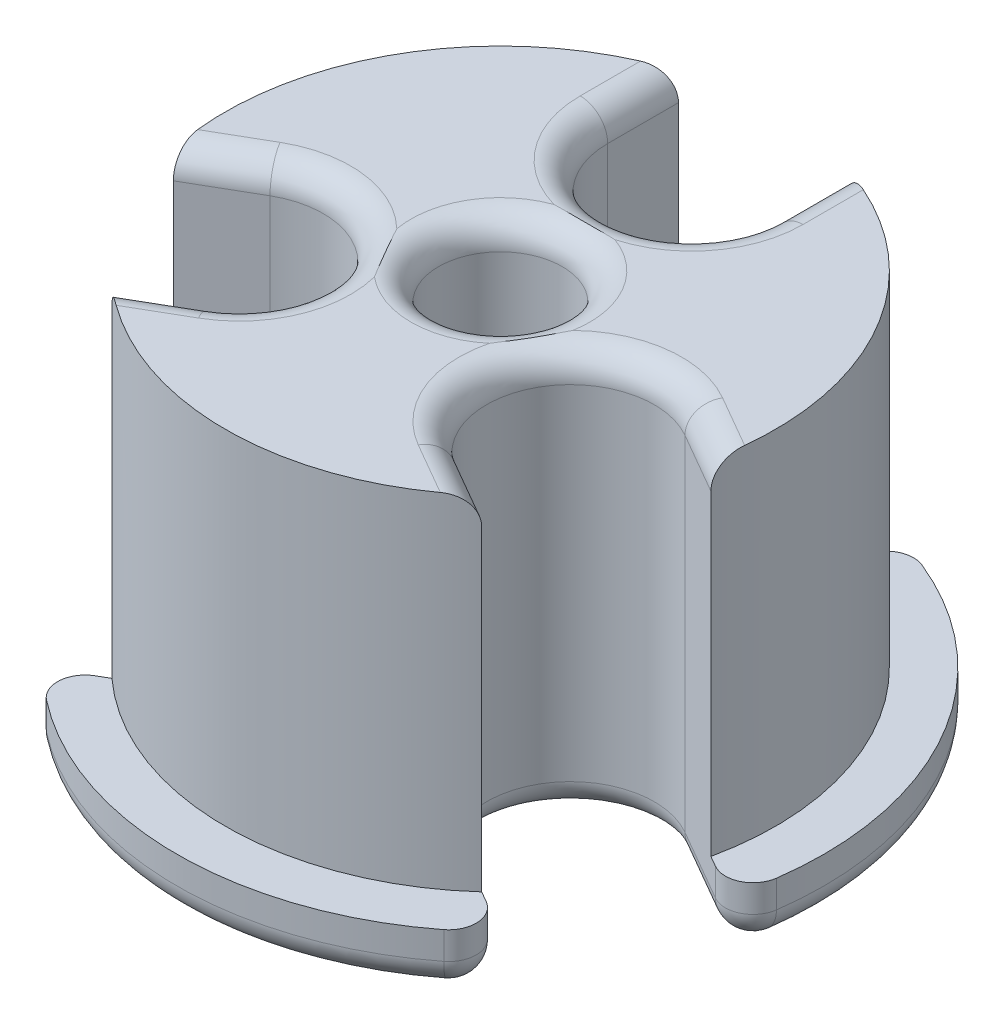
SolidWorks part; units mm, degrees
ref_plane "Front Plane" through (0, 0, 0) normal (0, 0, 1) x (1, 0, 0)
ref_plane "Top Plane" through (0, 0, 0) normal (0, 1, 0) x (1, 0, 0)
ref_plane "Right Plane" through (0, 0, 0) normal (1, 0, 0) x (0, 0, -1)
sketch "Sketch1" plane through (0, 0, 0) normal (0, 1, 0) x (1, 0, 0)
  circle A0 centre (0, 0) radius 11.76
  dimension "D1" = 23.52
extrude "Boss-Extrude1" add sketch "Sketch1" along normal blind 2
sketch "Sketch2" plane through (0, 2, 0) normal (0, 1, 0) x (1, 0, 0)
  circle A0 centre (0, 0) radius 10
  dimension "D1" = 20
extrude "Boss-Extrude2" add sketch "Sketch2" along normal blind 12.5
sketch "Sketch3" plane through (0, 14.5, 0) normal (0, 1, 0) x (1, 0, 0)
  circle A0 centre (0, 0) radius 2.25
  dimension "D1" = 4.5
extrude "Cut-Extrude1" cut sketch "Sketch3" against normal through all
sketch "Sketch4" plane through (0, 14.5, 0) normal (0, 1, 0) x (1, 0, 0)
  line L0 (-3.05, 6.95) -> (-3.05, 15)
  line L1 (-3.05, 15) -> (3.05, 15)
  line L2 (3.05, 15) -> (3.05, 6.95)
  arc A0 (-3.05, 6.95) -> (3.05, 6.95) centre (0, 6.95) ccw
  circle A1 centre (0, 0) radius 10 construction
  circle A2 centre (0, 0) radius 11.76 construction
  dimension "D1" = 6.1
  dimension "D2" = 15
extrude "Cut-Extrude3" cut sketch "Sketch4" against normal through all
pattern_circular "CirPattern1" count 3 over 360 about axis through (0, 14.5, 0) along (0, 1, 0) of "Cut-Extrude3"
fillet "Fillet1" radius 1 29 edges at (-3.05, 14.5, -8.2368) (3.05, 14.5, -8.2368) (8.6582, 14.5, 1.477) (5.6082, 14.5, 6.7598) (-5.6082, 14.5, 6.7598) (-8.6582, 14.5, 1.477) (-6.4024, 0, 7.2183) (-9.4524, 0, 1.9355) (-3.05, 0, -9.1538) (3.05, 0, -9.1538) (9.4524, 0, 1.9355) (6.4024, 0, 7.2183) (0, 14.5, -3.9) (0, 14.5, 2.25) (3.3775, 14.5, 1.95) (-3.3775, 14.5, 1.95) (0, 0, 2.25) (-3.3775, 0, 1.95) (0, 0, -3.9) (3.3775, 0, 1.95) (0, 0, 11.76) (10.1845, 0, -5.88) (-10.1845, 0, -5.88) (-11.361, 1, 3.0374) (-8.311, 1, 8.3202) (8.311, 1, 8.3202) (11.361, 1, 3.0374) (3.05, 1, -11.3576) (-3.05, 1, -11.3576)
